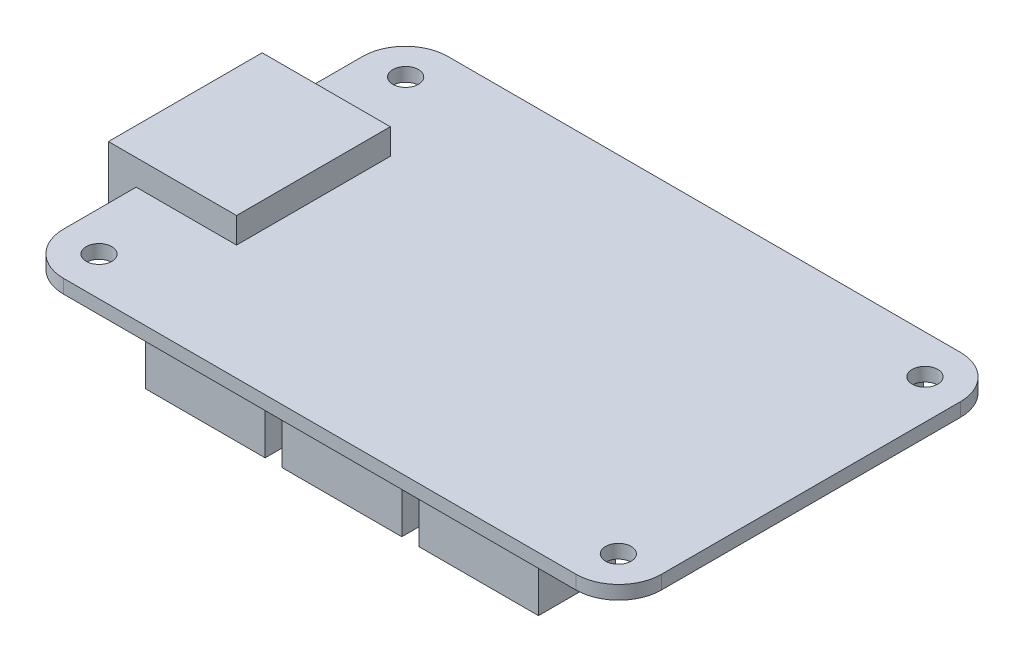
SolidWorks part; units mm, degrees
ref_plane "前视基准面" through (0, 0, 0) normal (0, 0, 1) x (1, 0, 0)
ref_plane "上视基准面" through (0, 0, 0) normal (0, 1, 0) x (1, 0, 0)
ref_plane "右视基准面" through (0, 0, 0) normal (1, 0, 0) x (0, 0, -1)
other "Configuration Table"
sketch "草图1" plane through (0, 0, 0) normal (0, 1, 0) x (1, 0, 0)
  line L0 (-58.822, 0) -> (62.6702, 0) construction
  line L1 (-30, 22.5) -> (30, 22.5)
  line L2 (-35, 17.5) -> (-35, -17.5)
  line L3 (-30, -22.5) -> (30, -22.5)
  line L4 (35, 17.5) -> (35, -17.5)
  line L5 (-35, 22.5) -> (35, -22.5) construction
  line L6 (-35, -22.5) -> (35, 22.5) construction
  line L7 (0, 44.0707) -> (0, -36.3743) construction
  circle A0 centre (-30.4, -17.95) radius 1.5
  circle A1 centre (30.4, -17.95) radius 1.5
  circle A2 centre (-30.4, 17.95) radius 1.5
  circle A3 centre (30.4, 17.95) radius 1.5
  circle A4 centre (-30.4, -17.95) radius 2.5
  circle A5 centre (-30.4, 17.95) radius 2.5
  circle A6 centre (30.4, 17.95) radius 2.5
  circle A7 centre (30.4, -17.95) radius 2.5
  arc A8 (30, -22.5) -> (35, -17.5) centre (30, -17.5) ccw
  arc A9 (30, 22.5) -> (35, 17.5) centre (30, 17.5) cw
  arc A10 (-30, 22.5) -> (-35, 17.5) centre (-30, 17.5) ccw
  arc A11 (-35, -17.5) -> (-30, -22.5) centre (-30, -17.5) ccw
  point P0 (0, 0)
  dimension "D3" = 3
  dimension "D4" = 60.8
  dimension "D5" = 35.9
  dimension "D7" = 5
  dimension "D1" = 70
  dimension "D2" = 45
  dimension "D6" = 1
extrude "凸台-拉伸1" add sketch "草图1" along normal blind 1.6 contours L2 A11 L3 A8 L4 A9 L1 A10 A7 A6 A4 A5 region at (0, 0, 0)
ref_plane "基准面1" through (0, 4.6, 0) normal (0, 1, 0) x (1, 0, 0)
sketch "草图2" plane through (0, 4.6, 0) normal (0, 1, 0) x (1, 0, 0)
  line L1 (-38.2502, 9) -> (-23.2502, 9)
  line L2 (-38.2502, 9) -> (-38.2502, -9)
  line L3 (-38.2502, -9) -> (-23.2502, -9)
  line L4 (-23.2502, 9) -> (-23.2502, -9)
  line L5 (-38.2502, 9) -> (-23.2502, -9) construction
  line L6 (-38.2502, -9) -> (-23.2502, 9) construction
  point P0 (-30.7502, 0)
  dimension "D1" = 18
  dimension "D2" = 15
extrude "凸台-拉伸2" add sketch "草图2" against normal blind 10
sketch "草图3" plane through (0, 0, 0) normal (0, -1, 0) x (1, 0, 0)
  line L0 (-30, -22.5) -> (30, -22.5) construction
  line L1 (-26.9, -15.45) -> (-16.9, -15.45)
  line L2 (-26.9, -15.45) -> (-26.9, -22.3)
  line L3 (-26.9, -22.3) -> (-16.9, -22.3)
  line L4 (-16.9, -15.45) -> (-16.9, -22.3)
  line L5 (-26.9, -15.45) -> (-16.9, -22.3) construction
  line L6 (-26.9, -22.3) -> (-16.9, -15.45) construction
  line L7 (-15.4, -15.45) -> (-5.4, -15.45)
  line L8 (-15.4, -15.45) -> (-15.4, -22.3)
  line L9 (-15.4, -22.3) -> (-5.4, -22.3)
  line L10 (-5.4, -15.45) -> (-5.4, -22.3)
  line L11 (-15.4, -15.45) -> (-5.4, -22.3) construction
  line L12 (-15.4, -22.3) -> (-5.4, -15.45) construction
  line L13 (-4.4, -13.45) -> (9.75, -13.45)
  line L14 (-4.4, -13.45) -> (-4.4, -22.3)
  line L15 (-4.4, -22.3) -> (9.75, -22.3)
  line L16 (9.75, -13.45) -> (9.75, -22.3)
  line L17 (-4.4, -13.45) -> (9.75, -22.3) construction
  line L18 (-4.4, -22.3) -> (9.75, -13.45) construction
  line L19 (11.75, -13.45) -> (25.9, -13.45)
  line L20 (11.75, -13.45) -> (11.75, -22.3)
  line L21 (11.75, -22.3) -> (25.9, -22.3)
  line L22 (25.9, -13.45) -> (25.9, -22.3)
  line L23 (11.75, -13.45) -> (25.9, -22.3) construction
  line L24 (11.75, -22.3) -> (25.9, -13.45) construction
  line L25 (-20.6, 22.3) -> (-6.6, 22.3)
  line L26 (-20.6, 22.3) -> (-20.6, 13.3)
  line L27 (-20.6, 13.3) -> (-6.6, 13.3)
  line L28 (-6.6, 22.3) -> (-6.6, 13.3)
  line L29 (-20.6, 22.3) -> (-6.6, 13.3) construction
  line L30 (-20.6, 13.3) -> (-6.6, 22.3) construction
  line L31 (-4.6, 22.3) -> (9.4, 22.3)
  line L32 (-4.6, 22.3) -> (-4.6, 13.3)
  line L33 (-4.6, 13.3) -> (9.4, 13.3)
  line L34 (9.4, 22.3) -> (9.4, 13.3)
  line L35 (-4.6, 22.3) -> (9.4, 13.3) construction
  line L36 (-4.6, 13.3) -> (9.4, 22.3) construction
  line L37 (11.4, 22.3) -> (25.4, 22.3)
  line L38 (11.4, 22.3) -> (11.4, 13.3)
  line L39 (11.4, 13.3) -> (25.4, 13.3)
  line L40 (25.4, 22.3) -> (25.4, 13.3)
  line L41 (11.4, 22.3) -> (25.4, 13.3) construction
  line L42 (11.4, 13.3) -> (25.4, 22.3) construction
  line L43 (-30, 22.5) -> (30, 22.5) construction
  circle A1 centre (30.4, -17.95) radius 2.5 construction
  circle A2 centre (30.4, 17.95) radius 2.5 construction
  circle A3 centre (-30.4, -17.95) radius 2.5 construction
  point P0 (-21.9, -18.875)
  point P5 (-10.4, -18.875)
  point P10 (2.675, -17.875)
  point P15 (18.825, -17.875)
  point P20 (-13.6, 17.8)
  point P25 (2.4, 17.8)
  point P30 (18.4, 17.8)
  dimension "D1" = 10
  dimension "D2" = 1.5
  dimension "D3" = 1
  dimension "D4" = 2
  dimension "D5" = 2
  dimension "D6" = 1
  dimension "D7" = 0.2
  dimension "D8" = 0
  dimension "D9" = 0
  dimension "D10" = 2
  dimension "D11" = 2.5
  dimension "D12" = 2
  dimension "D13" = 2
  dimension "D14" = 14
  dimension "D15" = 0.2
  dimension "D16" = 9
extrude "凸台-拉伸3" add sketch "草图3" along normal blind 5
extrude "凸台-拉伸4" add sketch "草图1<3>" along normal blind 1.6 contours A4 A0 | A5 A2 | A6 A3 | A7 A1 region at (-32.8293, 0, 17.95) region at (-32.8293, 0, -17.95) region at (27.9707, 0, -17.95) region at (27.9707, 0, 17.95)
sketch "草图1<3>" plane through (0, 0, 0) normal (0, 1, 0) x (1, 0, 0) same geometry as "草图1"
